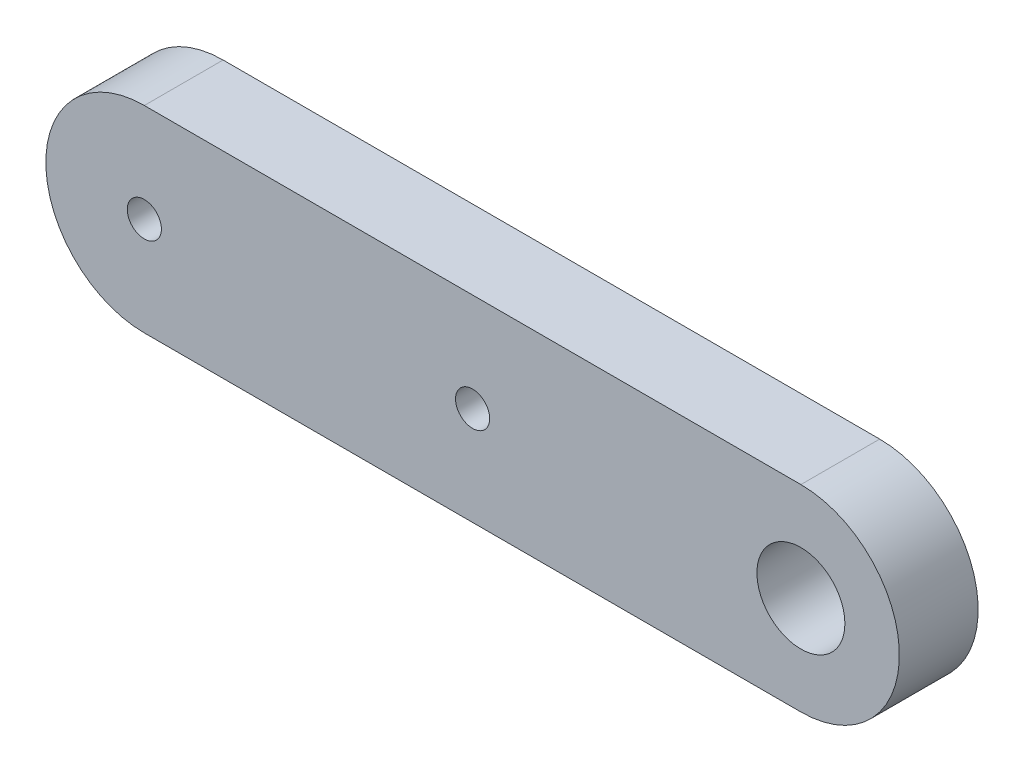
SolidWorks part; units mm, degrees
material "Pine"
ref_plane "Front Plane" through (0, 0, 0) normal (0, 0, 1) x (1, 0, 0)
ref_plane "Top Plane" through (0, 0, 0) normal (0, 1, 0) x (1, 0, 0)
ref_plane "Right Plane" through (0, 0, 0) normal (1, 0, 0) x (0, 0, -1)
sketch "Sketch1" plane through (0, 0, 0) normal (0, 0, 1) x (1, 0, 0)
  line L0 (0, 7.5) -> (50, 7.5)
  line L1 (50, -7.5) -> (0, -7.5)
  circle A0 centre (0, 0) radius 7.5
  circle A1 centre (50, 0) radius 7.5
  dimension "D1" = 50
  dimension "D2" = 15
extrude "Boss-Extrude1" add sketch "Sketch1" along normal blind 6 contours A1 L0 A0 L1 | A1 | A0 region at (25, 0, 0) region at (0, 0, 0) region at (50, 0, 0)
ref_plane "Plane1" through (0, 0, 3) normal (0, 0, 1) x (1, 0, 0)
sketch "Sketch2" plane through (0, 0, 6) normal (0, 0, 1) x (1, 0, 0)
  circle A0 centre (0, 0) radius 1.3
  circle A1 centre (50, 0) radius 1.3
  dimension "D1" = 2.6
extrude "Cut-Extrude1" cut sketch "Sketch2" against normal through all
pattern_linear "LPattern1" count 4 spacing 25 along (1, 0, 0) of "Cut-Extrude1"
sketch "Sketch3" plane through (0, 0, 6) normal (0, 0, 1) x (1, 0, 0)
  circle A0 centre (50, 0) radius 3.35
  dimension "D1" = 6.7
extrude "Cut-Extrude2" cut sketch "Sketch3" against normal through all
